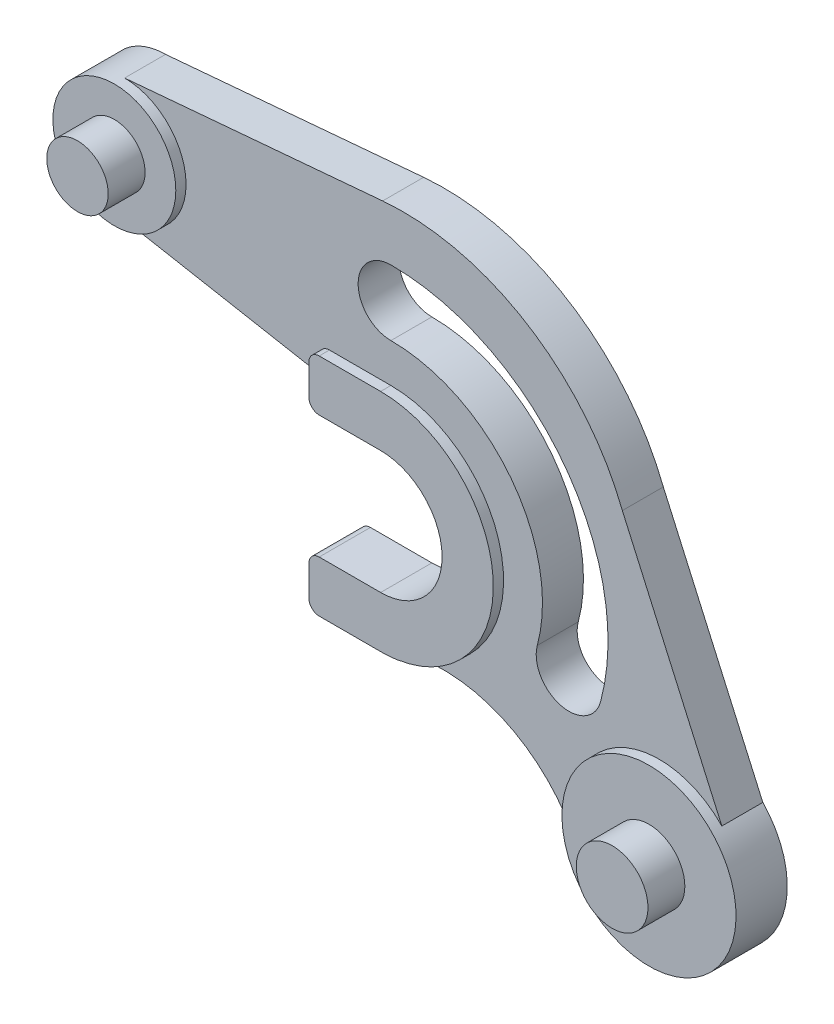
SolidWorks part; units mm, degrees
ref_plane "정면" through (0, 0, 0) normal (0, 0, 1) x (1, 0, 0)
ref_plane "윗면" through (0, 0, 0) normal (0, 1, 0) x (1, 0, 0)
ref_plane "우측면" through (0, 0, 0) normal (1, 0, 0) x (0, 0, -1)
sketch "Sketch1" plane through (0, 0, 0) normal (0, 0, 1) x (1, 0, 0)
  line L0 (0, 90) -> (0, -242.0593) construction
  line L1 (0, 90) -> (-130, 90) construction
  line L2 (86.9321, -23.2981) -> (0, 0) construction
  line L3 (0, 90) -> (0, 0) construction
  line L4 (-35, 42.5) -> (-130, 60)
  line L5 (-130, 120) -> (-4.0208, 131.0218)
  line L6 (-30, 30) -> (0, 30)
  line L7 (0, -30) -> (-30, -30)
  line L8 (-30, 55) -> (0, 55)
  line L9 (0, -55) -> (-30, -55)
  line L10 (-35, 35) -> (-35, 50)
  line L11 (-35, -35) -> (-35, -50)
  line L12 (112.9933, 58.6244) -> (161.5653, -50.4701)
  circle A0 centre (-130, 90) radius 30
  circle A1 centre (-130, 90) radius 15
  circle A2 centre (131, -80) radius 42.5
  circle A3 centre (131, -80) radius 17.5
  arc A4 (0, 90) -> (86.9321, -23.2981) centre (0, 0) cw construction
  arc A5 (102.3867, -27.44) -> (0, 106) centre (0, 0) ccw
  arc A6 (71.4775, -19.1562) -> (0, 74) centre (0, 0) ccw
  arc A7 (71.4775, -19.1562) -> (102.3867, -27.44) centre (86.9321, -23.2981) ccw
  arc A8 (0, 106) -> (0, 74) centre (0, 90) ccw
  arc A9 (-4.0208, 131.0218) -> (112.9933, 58.6244) centre (6.0021, 16.4594) cw
  arc A10 (0, 30) -> (0, -30) centre (0, 0) cw
  arc A11 (0, 55) -> (0, -55) centre (0, 0) cw
  arc A12 (8.3571, -54.3614) -> (91.8773, -96.6031) centre (25.4218, -124.3099) cw
  arc A13 (-35, -50) -> (-30, -55) centre (-30, -50) ccw
  arc A14 (-30, -30) -> (-35, -35) centre (-30, -35) ccw
  arc A15 (-30, 30) -> (-35, 35) centre (-30, 35) cw
  arc A16 (-30, 55) -> (-35, 50) centre (-30, 50) ccw
  point P10 (71.4032, 54.7867)
  point P39 (8.9385, -54.2688)
  point P40 (90.4093, -92.5955)
  point P41 (4.5858, -55)
  point P42 (91.8773, -96.6031)
  point P43 (0.9355, -55)
  point P44 (0, 0)
  point P45 (8.3571, -54.3614)
  dimension "D1" = 60
  dimension "D3" = 85
  dimension "D5" = 16
  dimension "D6" = 130
  dimension "D11" = 72
  dimension "D13" = 131
  dimension "D9" = 55
  dimension "D16" = 105.003
  dimension "D17" = 90
  dimension "D18" = 115
  dimension "D8" = 5
  dimension "D10" = 35
  dimension "D12" = 71
  dimension "D14" = 5
  dimension "D15" = 80
  dimension "D2" = 15
  dimension "D4" = 25
extrude "Boss-Extrude4" add sketch "Sketch1" along normal blind 20 contours A16 L8 A11 A12 A2 L12 A9 L5 A0 L4 L10 A8 A5 A7 A6 region at (21.6342, 51.3167, 0)
extrude "Boss-Extrude5" add sketch "Sketch1<5>" along normal blind 25 contours A0 A1 | A2 A12 A3 | L8 A16 L10 A15 L6 A10 L7 A14 L11 A13 L9 A11 A12 region at (-33.5787, 46.25, 0) region at (-159.1515, 90, 0) region at (169.289, -64.5252, 0)
sketch "Sketch1<5>" plane through (0, 0, 0) normal (0, 0, 1) x (1, 0, 0) same geometry as "Sketch1"
extrude "Boss-Extrude6" add sketch "Sketch1<6>" along normal blind 43 contours A1 | A3 region at (-130, 90, 0) region at (131, -80, 0)
sketch "Sketch1<6>" plane through (0, 0, 0) normal (0, 0, 1) x (1, 0, 0) same geometry as "Sketch1"
